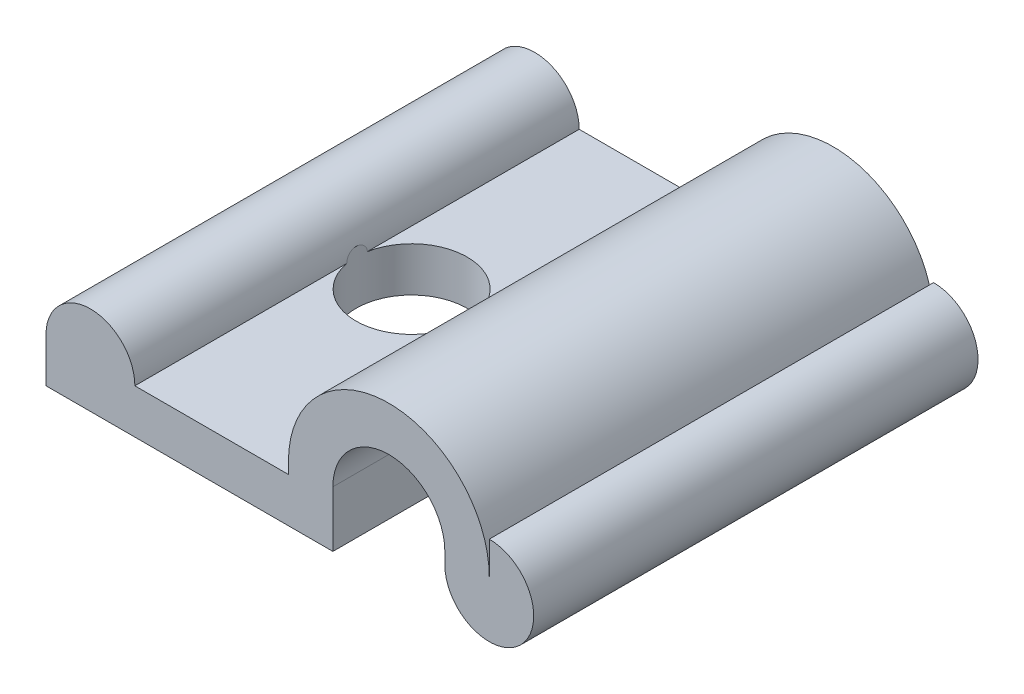
SolidWorks part; units mm, degrees
ref_plane "Front" through (0, 0, 0) normal (0, 0, 1) x (1, 0, 0)
ref_plane "Top" through (0, 0, 0) normal (0, 1, 0) x (1, 0, 0)
ref_plane "Right" through (0, 0, 0) normal (1, 0, 0) x (0, 0, -1)
sketch "Sketch1" plane through (0, 0, 0) normal (0, 0, 1) x (1, 0, 0)
  line L0 (-14.52, -0.66) -> (-5.74, -0.66)
  line L1 (5.74, 0) -> (5.74, 1.88)
  line L2 (3.2, 0) -> (3.2, -0.66)
  line L3 (-3.2, 0) -> (-3.2, -3.2)
  line L4 (-5.74, 0) -> (-5.74, -0.66)
  line L5 (-6.9, -0.66) -> (-6.9, -8.7588) construction
  line L6 (-3.2, -3.2) -> (-19.6, -3.2)
  line L7 (-19.6, -3.2) -> (-19.6, -0.66)
  line L8 (-14.52, -0.66) -> (-14.52, -3.2) construction
  line L9 (3.2, 0) -> (5.74, 0) construction
  arc A0 (3.2, 0) -> (-3.2, 0) centre (0, 0) ccw
  arc A1 (5.74, 0) -> (-5.74, 0) centre (0, 0) ccw
  arc A2 (3.2, -0.66) -> (5.74, 1.88) centre (5.74, -0.66) ccw
  arc A3 (-14.52, -0.66) -> (-19.6, -0.66) centre (-17.06, -0.66) ccw
  dimension "D1" = 6.4
  dimension "D2" = 2.54
  dimension "D4" = 2.54
  dimension "D6" = 27.88
  dimension "D3" = 8.94
  dimension "D8" = 6.9
  dimension "D9" = 12.7
extrude "Base-Extrude" add sketch "Sketch1" along normal mid plane 25.4
sketch "Sketch6" plane through (0, 0, 12.7) normal (0, 0, 1) x (1, 0, 0)
  point P0 (0, 0)
sketch "Sketch7" plane through (0, 0, -12.7) normal (0, 0, -1) x (-1, 0, 0)
  point P0 (0, 0)
ref_axis "Clip Axis" through (0, 0, 12.7) along (0, 0, -1)
other "RPoint1"
ref_axis "Axis1" through (0, 0, 7.7) along (0, 0, 1)
other "RPoint2"
ref_axis "Axis2" through (0, 0, -7.7) along (0, 0, -1)
sketch "FilterSketch" plane through (0, 0, 0) normal (0, 0, 1) x (1, 0, 0)
  circle A0 centre (0, 0) radius 3.2
  circle A1 centre (0, 0) radius 3.2
  circle A2 centre (0, 0) radius 2.35
  dimension "NominalDiameter" = 6.4
  dimension "InnerDiameter" = 4.7
  dimension "OuterDiameter" = 6.4
sketch "Sketch9" plane through (0, -3.2, 0) normal (0, -1, 0) x (1, 0, 0)
  line L0 (-19.6, 12.7) -> (-3.2, -12.7) construction
  circle A0 centre (-11.4, 0) radius 3.175
  dimension "D1" = 6.35
extrude "Cut-Extrude1" cut sketch "Sketch9" against normal through all
ref_axis "Axis of Rotation" through (-11.4, 9.968, 0) along (0, -1, 0)
